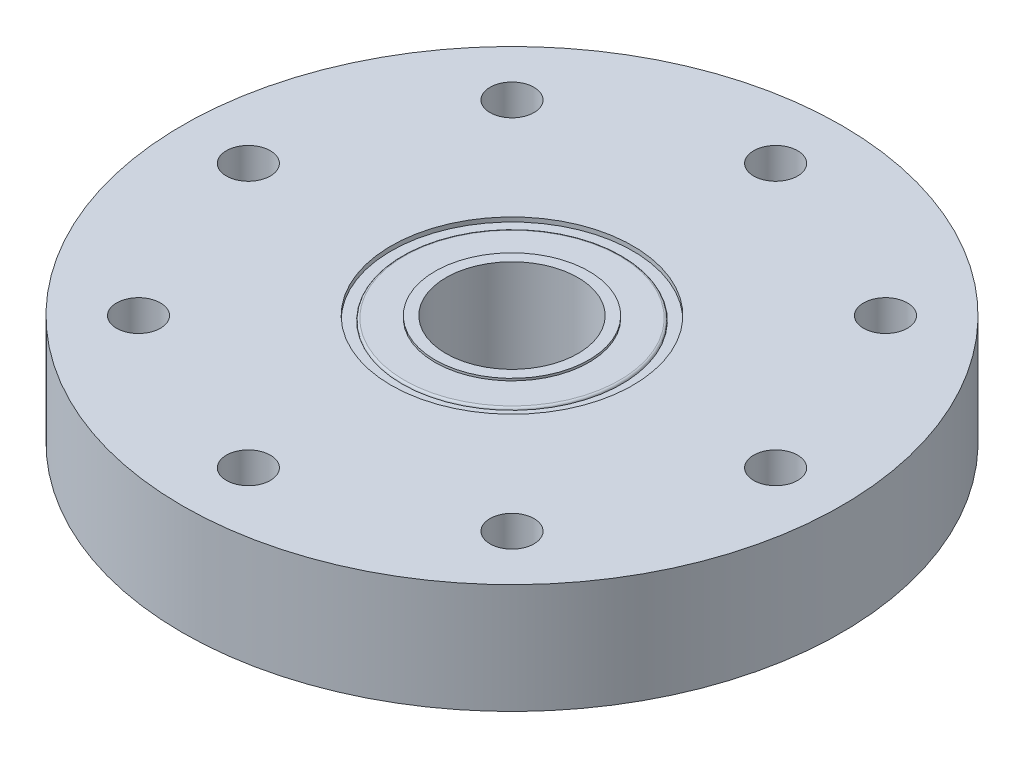
SolidWorks part; units mm, degrees
ref_plane "Front Plane" through (0, 0, 0) normal (0, 0, 1) x (1, 0, 0)
ref_plane "Top Plane" through (0, 0, 0) normal (0, 1, 0) x (1, 0, 0)
ref_plane "Right Plane" through (0, 0, 0) normal (1, 0, 0) x (0, 0, -1)
sketch "Sketch1" plane through (0, 0, 0) normal (0, 1, 0) x (1, 0, 0)
  line L0 (0, 12) -> (0, -12) construction
  line L1 (-12, 0) -> (12, 0) construction
  line L6 (8.5, 8.5) -> (-8.5, 8.5) construction
  circle A0 centre (0, 0) radius 15
  circle A2 centre (0, 12) radius 1
  circle A3 centre (0, -12) radius 1
  circle A4 centre (0, 0) radius 3
  circle A5 centre (-12, 0) radius 1
  circle A6 centre (12, 0) radius 1
  circle A7 centre (8.5, 8.5) radius 1
  circle A8 centre (8.5, -8.5) radius 1
  circle A9 centre (-8.5, -8.5) radius 1
  circle A10 centre (-8.5, 8.5) radius 1
  point P6 (0, 0)
  point P12 (0, 0)
  point P20 (0, 8.5)
  dimension "D1" = 4
extrude "Boss-Extrude1" add sketch "Sketch1" along normal blind 5
sketch "Sketch4" plane through (0, 5, 0) normal (0, 1, 0) x (1, 0, 0)
  line L0 (0, 5) -> (0, 5.5) construction
  line L1 (0, -3) -> (0, -3.5) construction
  circle A0 centre (0, 0) radius 5
  circle A1 centre (0, 0) radius 5.5
  circle A2 centre (0, 0) radius 3.5
  circle A3 centre (0, 0) radius 3 construction
extrude "Cut-Extrude1" cut sketch "Sketch4" against normal blind 0.2 contours A1 A0 region at (-5.3444, 5, 0)
extrude "Cut-Extrude2" cut sketch "Sketch4<3>" against normal blind 0.1 contours A0 A2 region at (-4.8586, 5, 0)
sketch "Sketch4<3>" plane through (0, 5, 0) normal (0, 1, 0) x (1, 0, 0) same geometry as "Sketch4"
sketch "Sketch5" plane through (0, 0, 0) normal (0, -1, 0) x (1, 0, 0)
  circle A0 centre (0, 0) radius 3.5
  circle A2 centre (0, 0) radius 5
  circle A3 centre (0, 0) radius 5.75
extrude "Cut-Extrude3" cut sketch "Sketch5" against normal blind 0.1 contours A2 A0 region at (-4.8586, 0, 0)
extrude "Cut-Extrude4" cut sketch "Sketch5<3>" against normal blind 0.2 contours A3 A2 region at (-5.5874, 0, 0)
sketch "Sketch5<3>" plane through (0, 0, 0) normal (0, -1, 0) x (1, 0, 0) same geometry as "Sketch5"
fillet "Fillet1" radius 0.1 2 edges at (0, 4.9, 5) (0, 0.1, -5)
